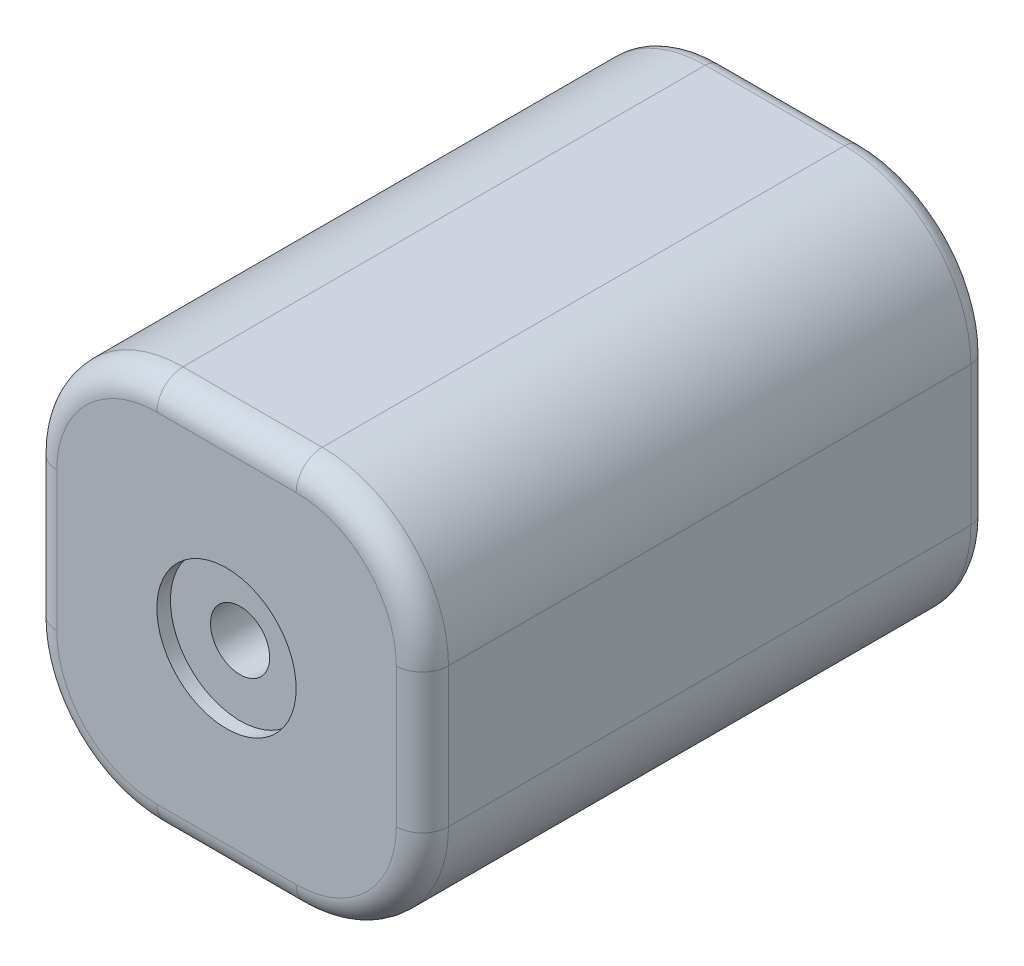
SolidWorks part; units mm, degrees
ref_plane "Front Plane" through (0, 0, 0) normal (0, 0, 1) x (1, 0, 0)
ref_plane "Top Plane" through (0, 0, 0) normal (0, 1, 0) x (1, 0, 0)
ref_plane "Right Plane" through (0, 0, 0) normal (1, 0, 0) x (0, 0, -1)
sketch "Sketch1" plane through (0, 0, 0) normal (0, 0, 1) x (1, 0, 0)
  line L1 (-8, 18) -> (8, 18)
  line L2 (-18, 8) -> (-18, -8)
  line L3 (-8, -18) -> (8, -18)
  line L4 (18, 8) -> (18, -8)
  line L5 (-18, 18) -> (18, -18) construction
  line L6 (-18, -18) -> (18, 18) construction
  line L7 (-8, 22.5) -> (8, 22.5)
  line L8 (-22.5, 8) -> (-22.5, -8)
  line L9 (-8, -22.5) -> (8, -22.5)
  line L10 (22.5, 8) -> (22.5, -8)
  line L11 (-22.5, 22.5) -> (22.5, -22.5) construction
  line L12 (-22.5, -22.5) -> (22.5, 22.5) construction
  arc A0 (8, -18) -> (18, -8) centre (8, -8) ccw
  arc A1 (-18, -8) -> (-8, -18) centre (-8, -8) ccw
  arc A2 (-8, 18) -> (-18, 8) centre (-8, 8) ccw
  arc A3 (8, 18) -> (18, 8) centre (8, 8) cw
  arc A4 (8, 22.5) -> (22.5, 8) centre (8, 8) cw
  arc A5 (8, -22.5) -> (22.5, -8) centre (8, -8) ccw
  arc A6 (-22.5, -8) -> (-8, -22.5) centre (-8, -8) ccw
  arc A7 (-8, 22.5) -> (-22.5, 8) centre (-8, 8) ccw
  point P0 (0, 0)
  point P18 (0, 0)
  dimension "D3" = 10
  dimension "D6" = 14.5
  dimension "D1" = 36
  dimension "D2" = 36
  dimension "D4" = 45
  dimension "D5" = 45
extrude "Boss-Extrude1" add sketch "Sketch1" along normal blind 65 contours A3 L1 A2 L2 A1 L3 A0 L4 | L7 A4 L10 A5 L9 A6 L8 A7 region at (0, 0, 0)
fillet "Fillet1" radius 2 16 edges at (-22.5, 0, 0) (-18.253, -18.253, 0) (0, -22.5, 0) (18.253, -18.253, 0) (22.5, 0, 0) (18.253, 18.253, 0) (0, 22.5, 0) (-18.253, 18.253, 0) (15.0711, -15.0711, 0) (0, -18, 0) (-15.0711, -15.0711, 0) (-18, 0, 0) (-15.0711, 15.0711, 0) (0, 18, 0) (15.0711, 15.0711, 0) (18, 0, 0)
sketch "Sketch2" plane through (0, 0, 65) normal (0, 0, 1) x (1, 0, 0)
  line L1 (8, -22.5) -> (-8, -22.5)
  line L2 (22.5, -8) -> (22.5, 8)
  line L3 (8, 22.5) -> (-8, 22.5)
  line L4 (-22.5, -8) -> (-22.5, 8)
  line L5 (22.5, -22.5) -> (-22.5, 22.5) construction
  line L6 (22.5, 22.5) -> (-22.5, -22.5) construction
  arc A0 (-8, -22.5) -> (-22.5, -8) centre (-8, -8) cw
  arc A1 (8, -22.5) -> (22.5, -8) centre (8, -8) ccw
  arc A2 (22.5, 8) -> (8, 22.5) centre (8, 8) ccw
  arc A3 (-8, 22.5) -> (-22.5, 8) centre (-8, 8) ccw
  point P0 (0, 0)
  dimension "D3" = 14.5
  dimension "D1" = 45
  dimension "D2" = 45
extrude "Boss-Extrude2" add sketch "Sketch2" against normal blind 10
sketch "Sketch3" plane through (0, 0, 65) normal (0, 0, 1) x (1, 0, 0)
  circle A0 centre (0, 0) radius 3.4
  dimension "D1" = 6.8
extrude "Cut-Extrude1" cut sketch "Sketch3" against normal through all contours A0
fillet "Fillet2" radius 3 8 edges at (0, 22.5, 65) (18.253, 18.253, 65) (22.5, 0, 65) (18.253, -18.253, 65) (0, -22.5, 65) (-18.253, -18.253, 65) (-22.5, 0, 65) (-18.253, 18.253, 65)
sketch "Sketch4" plane through (0, 0, 65) normal (0, 0, 1) x (1, 0, 0)
  circle A0 centre (0, 0) radius 8
  dimension "D1" = 16
extrude "Cut-Extrude2" cut sketch "Sketch4" against normal blind 1.56
